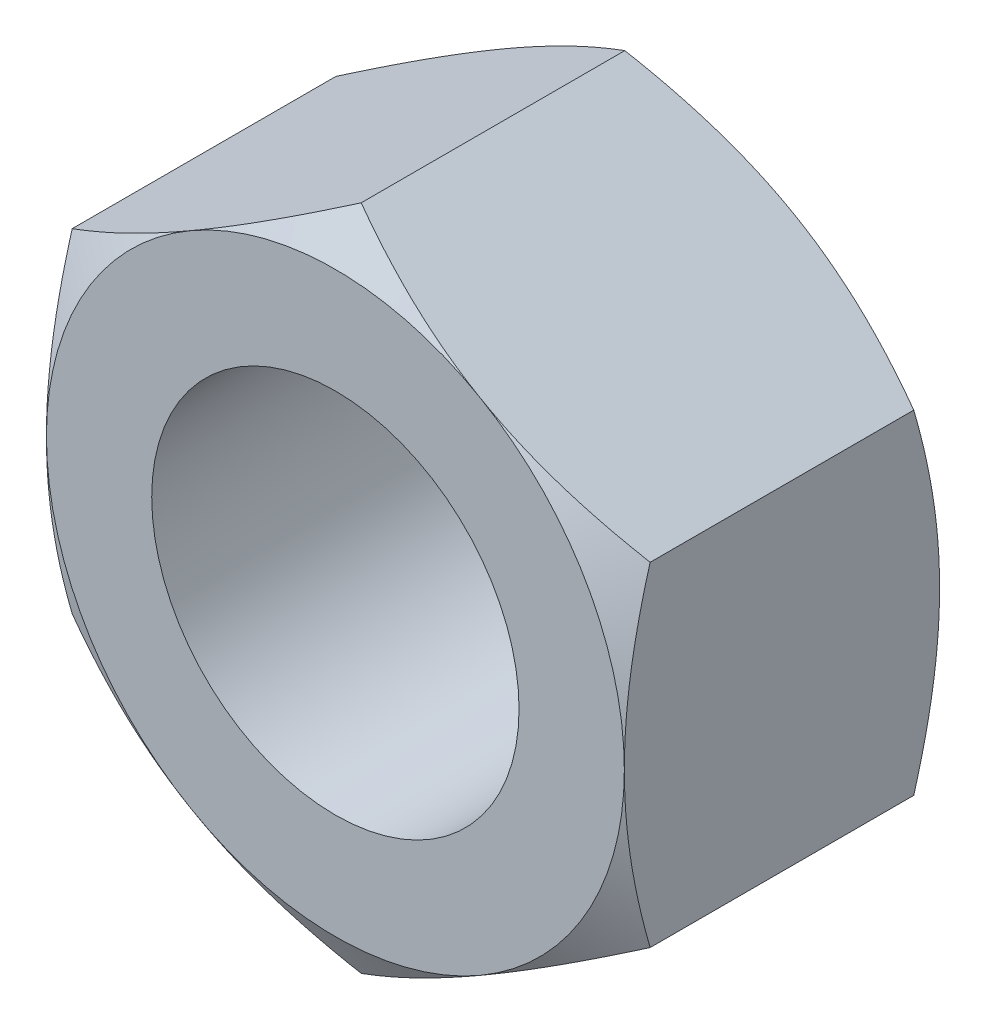
SolidWorks part; units mm, degrees
ref_plane "Front" through (0, 0, 0) normal (0, 0, 1) x (1, 0, 0)
ref_plane "Top" through (0, 0, 0) normal (0, 1, 0) x (1, 0, 0)
ref_plane "Right" through (0, 0, 0) normal (1, 0, 0) x (0, 0, -1)
sketch "Sketch1" plane through (0, 0, 0) normal (0, 0, 1) x (1, 0, 0)
  line L1 (-8.7312, 5.041) -> (-8.7312, -5.041)
  line L2 (-8.7312, -5.041) -> (0, -10.082)
  line L3 (0, -10.082) -> (8.7312, -5.041)
  line L4 (8.7312, -5.041) -> (8.7312, 5.041)
  line L5 (8.7312, 5.041) -> (0, 10.082)
  line L6 (0, 10.082) -> (-8.7312, 5.041)
  circle A0 centre (0, 0) radius 8.7312 construction
  circle A1 centre (0, 0) radius 5.5499
  point P10 (0, 5.5499)
  dimension "hex" = 17.4625
  dimension "dia" = 11.0998
extrude "Extrude1" add sketch "Sketch1" along normal mid plane 9.525
sketch "Sketch4" plane through (0, 0, -4.7625) normal (0, 0, -1) x (-1, 0, 0)
  circle A0 centre (0, 0) radius 5.5499 construction
  circle A1 centre (0, 0) radius 5.5499
curve "Helix/Spiral3" pitch 1.27 height 11.43 turns 9
sketch "Sketch3" plane through (0, 0, 0) normal (1, 0, 0) x (0, 0, -1)
  line L0 (4.7625, 5.5499) -> (5.8737, 5.5499)
  line L1 (5.8737, 5.5499) -> (5.3975, 4.725)
  line L2 (5.3975, 4.725) -> (5.2387, 4.725)
  line L3 (5.2387, 4.725) -> (4.7625, 5.5499)
  line L4 (5.0006, 5.1375) -> (5.6356, 5.1375) construction
  dimension "D1" = 60
  dimension "D2" = 0.635
  dimension "D3" = 0.1588
sweep "Sweep1" [suppressed] add profiles "Sketch3" path "Helix/Spiral3"
sketch "Sketch6" [suppressed] plane through (0, 0, 0) normal (1, 0, 0) x (0, 0, -1)
  line L0 (-5.08, 5.8674) -> (-4.445, 5.2324)
  line L1 (-4.445, 5.2324) -> (-4.445, 0) construction
  line L2 (6.6607, 0) -> (-6.6607, 0) construction
  line L3 (-4.445, 0) -> (-6.6675, 0)
  line L4 (-6.6675, 0) -> (-6.6675, 5.8674)
  line L5 (-6.6675, 5.8674) -> (-5.08, 5.8674)
  line L6 (-4.445, 5.2324) -> (0.7874, 0)
  line L7 (0.7874, 0) -> (-4.445, 0)
  line L8 (-4.7625, -5.041) -> (-4.7625, 5.041) construction
  point P2 (-4.7625, 5.5499)
  dimension "D2" = 0.635
  dimension "D1" = 45
revolve "Cut-Revolve1" [suppressed] cut sketch "Sketch6" angle 360 about L3
sketch "Sketch7" plane through (0, 0, 4.7625) normal (0, 0, 1) x (1, 0, 0)
  circle A0 centre (0, 0) radius 8.7312 construction
  circle A1 centre (0, 0) radius 8.7312
extrude "Extrude2" cut sketch "Sketch7" against normal blind 25.4 draft 60 flip side to cut
mirror "Mirror1" about plane through (0, 0, 0) normal (0, 0, 1) of "Extrude2", "Cut-Revolve1"
sketch "Sketch8" [suppressed] plane through (0, 0, 4.7625) normal (0, 0, 1) x (1, 0, 0)
  line L0 (-3.9244, 3.9244) -> (0, 0) construction
  line L1 (0, -6.6607) -> (0, 6.6607) construction
  circle A0 centre (0, 0) radius 5.5499 construction
  point P0 (-3.9244, 3.9244)
  dimension "D1" = 45
equation "\"D3@Helix/Spiral3\" = \"length@Extrude1\" * 1.2"
equation "\"D2@Sketch3\" = \"D4@Helix/Spiral3\" * .5"
equation "\"D3@Sketch3\" = \"D4@Helix/Spiral3\" * .125"
equation "\"D2@Sketch6\" = \"D4@Helix/Spiral3\" * .5"
